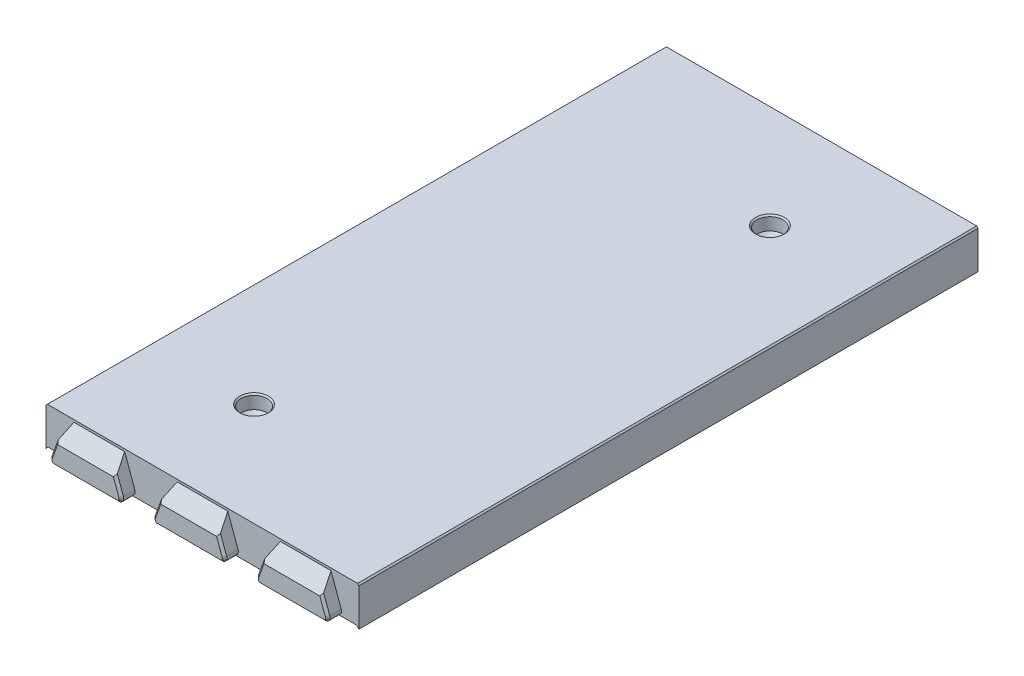
SolidWorks part; units mm, degrees
ref_plane "Front Plane" through (0, 0, 0) normal (0, 0, 1) x (1, 0, 0)
ref_plane "Top Plane" through (0, 0, 0) normal (0, 1, 0) x (1, 0, 0)
ref_plane "Right Plane" through (0, 0, 0) normal (1, 0, 0) x (0, 0, -1)
sketch "Sketch1" plane through (0, 0, 0) normal (0, 0, 1) x (1, 0, 0)
  line L0 (0, 0) -> (0, 8) construction
  line L1 (-34.125, 0) -> (0, 0) construction
  line L2 (-34.125, 0) -> (-34.125, 8)
  line L3 (-34.125, 8) -> (34.125, 8)
  line L5 (-34.125, 0) -> (-32.125, 0)
  line L6 (-32.125, 0) -> (-32.125, 6)
  line L7 (-32.125, 6) -> (32.125, 6)
  line L9 (32.125, 0) -> (32.125, 6)
  line L10 (34.125, 0) -> (32.125, 0)
  line L11 (34.125, 0) -> (34.125, 8)
  point P8 (0, 6)
  dimension "D2" = 6
  dimension "D1" = 34.125
  dimension "D3" = 2
  dimension "D4" = 2
extrude "Boss-Extrude1" add sketch "Sketch1" against normal blind 67.5
sketch "Sketch7" plane through (0, 0, 0) normal (0, 0, 1) x (1, 0, 0)
  line L2 (-32.125, 0) -> (32.125, 0)
  line L13 (-32.125, 0) -> (-32.125, 6)
  line L15 (-32.125, 6) -> (32.125, 6)
  line L16 (32.125, 0) -> (32.125, 6)
  line M3 (-32.125, 0) -> (-32.125, 6)
  line M4 (-32.125, 6) -> (32.125, 6)
  line M5 (32.125, 6) -> (32.125, 0)
extrude "Boss-Extrude7" add sketch "Sketch7" against normal blind 1 contours M4 M3 | M5 region at (0, 3, 0)
sketch "Sketch2" plane through (0, 0, 0) normal (0, 0, 1) x (1, 0, 0)
  line L14 (17.1618, 8) -> (14.25, 0)
  line L15 (34.125, 8) -> (-34.125, 8) construction
  line L16 (-34.125, 0) -> (34.125, 0) construction
  line L17 (14.25, 0) -> (30.75, 0)
  line L18 (17.1618, 8) -> (27.8382, 8)
  line L19 (-34.125, 0) -> (34.125, 0) construction
  line L21 (27.8382, 8) -> (30.75, 0)
  line L24 (11.25, 0) -> (11.25, 8) construction
  line L27 (-5.3382, 8) -> (-8.25, 0)
  line L28 (-5.3382, 8) -> (5.3382, 8)
  line L29 (-8.25, 0) -> (8.25, 0)
  line L30 (5.3382, 8) -> (8.25, 0)
  line L31 (-27.8382, 8) -> (-30.75, 0)
  line L32 (-27.8382, 8) -> (-17.1618, 8)
  line L33 (-30.75, 0) -> (-14.25, 0)
  line L34 (-17.1618, 8) -> (-14.25, 0)
  line L39 (17.1618, 8) -> (-5.3382, 8) construction
  line L40 (33.75, 8) -> (33.75, 0) construction
  line L41 (34.125, 0) -> (34.125, 8) construction
  line L42 (-33.75, 8) -> (-33.75, 0) construction
  line L43 (-34.125, 8) -> (-34.125, 0) construction
  point P22 (22.5, 8)
  point P23 (0, 8)
  dimension "D1" = 70
  dimension "D2" = 0.375
  dimension "D3" = 3
  dimension "D4" = 3
  dimension "D5" = 70
  dimension "D7" = 22.5
  dimension "D8" = 22.5
  dimension "D9" = 0.375
  dimension "D10" = 16.5
  dimension "D11" = 8
  dimension "D6" = 3
extrude "Boss-Extrude4" add sketch "Sketch2" along normal blind 3
sketch "Sketch8" plane through (0, 0, 0) normal (0, -1, 0) x (1, 0, 0)
  line L0 (-34.125, -22.5) -> (34.125, -22.5) construction
  line L2 (34.125, -67.5) -> (34.125, 0) construction
  line L3 (-34.125, 0) -> (-30.75, 0) construction
  line L4 (-32.75, -24.9559) -> (-32.75, -20.0441)
  line L5 (-32.75, -20.0441) -> (-28.75, -21.5)
  line L6 (-28.75, -21.5) -> (-28.75, -23.5)
  line L7 (-32.75, -67.5) -> (-32.75, -65.0441)
  line L8 (-32.75, -65.0441) -> (-28.75, -66.5)
  line L9 (-28.75, -66.5) -> (-28.75, -67.5)
  line L10 (-32.125, -67.5) -> (32.125, -67.5) construction
  line L11 (-28.75, -67.5) -> (-32.75, -67.5)
  line L12 (-32.75, -24.9559) -> (-28.75, -23.5)
  line L13 (0, -67.5) -> (0, 0) construction
  line L23 (-34.125, -67.5) -> (-34.125, 0) construction
  line L24 (32.75, -24.9559) -> (28.75, -23.5)
  line L25 (28.75, -21.5) -> (28.75, -23.5)
  line L26 (32.75, -20.0441) -> (28.75, -21.5)
  line L27 (32.75, -24.9559) -> (32.75, -20.0441)
  line L28 (-34.125, -67.5) -> (-32.125, -67.5) construction
  line L29 (28.75, -67.5) -> (32.75, -67.5)
  line L30 (28.75, -66.5) -> (28.75, -67.5)
  line L31 (32.75, -65.0441) -> (28.75, -66.5)
  line L32 (32.75, -67.5) -> (32.75, -65.0441)
  point P19 (-28.75, -22.5)
  point P32 (28.75, -22.5)
  dimension "D1" = 22.5
  dimension "D3" = 70
  dimension "D4" = 4
  dimension "D5" = 1.375
  dimension "D6" = 4
  dimension "D7" = 70
  dimension "D8" = 1
  dimension "D9" = 1
extrude "Boss-Extrude8" add sketch "Sketch8" against normal up to next and the other way blind 2
chamfer "Chamfer4" distance 0.5 angle 45 14 edges at (-28.75, -2, -67) (-30.75, -2, -65.7721) (-32.75, -2, -66.2721) (-30.75, -2, -24.2279) (-28.75, -2, -22.5) (-30.75, -2, -20.7721) (28.75, -2, -22.5) (30.75, -2, -24.2279) (30.75, -2, -20.7721) (32.75, -2, -22.5) (28.75, -2, -67) (32.75, -2, -66.2721) (30.75, -2, -65.7721) (-32.75, -2, -22.5)
fillet "Fillet4" radius 1 6 edges at (-30.75, 0, 1.5) (-14.25, 0, 1.5) (-8.25, 0, 1.5) (8.25, 0, 1.5) (14.25, 0, 1.5) (30.75, 0, 1.5)
chamfer "Chamfer6" distance 0.5 angle 45 15 edges at (15.9501, 4.671, 3) (29.0499, 4.671, 3) (22.5, 0, 3) (-29.0499, 4.671, 3) (-22.5, 0, 3) (-15.9501, 4.671, 3) (-6.5499, 4.671, 3) (6.5499, 4.671, 3) (0, 0, 3) (-30.141, 0.4264, 3) (-14.859, 0.4264, 3) (-7.641, 0.4264, 3) (7.641, 0.4264, 3) (14.859, 0.4264, 3) (30.141, 0.4264, 3)
fillet "Fillet2" radius 2 23 edges at (0, 6, -1) (-32.125, 3, -65.2716) (-30.4375, 6, -65.8858) (-28.75, 6, -67) (-32.125, 3, -1) (-30.4375, 6, -20.8858) (-32.125, 3, -20.2716) (-32.125, 6, -45) (-28.75, 6, -22.5) (-30.4375, 6, -24.1142) (-32.125, 3, -24.7284) (32.125, 6, -10.6358) (32.125, 3, -1) (-32.125, 6, -10.6358) (32.125, 3, -24.7284) (32.125, 3, -20.2716) (32.125, 3, -65.2716) (28.75, 6, -67) (30.4375, 6, -65.8858) (30.4375, 6, -20.8858) (28.75, 6, -22.5) (32.125, 6, -45) (30.4375, 6, -24.1142)
mirror "Mirror2" about plane through (0, 0, -67.5) normal (0, 0, 1) of "Fillet4", "Boss-Extrude1", "Boss-Extrude7", "Boss-Extrude4", "Boss-Extrude8", "Chamfer4", "Fillet2", "Chamfer6"
sketch "Sketch9" plane through (0, 0, 0) normal (0, 1, 0) x (1, 0, 0)
  line L16 (0, 67.5) -> (0, 138) construction
  line L17 (-34.125, 67.5) -> (34.125, 67.5) construction
  line L18 (-34.125, 70.4563) -> (-34.125, 64.5437) construction
  line L20 (34.125, 135) -> (34.125, 0) construction
  line L24 (4.8061, 138) -> (-4.8061, 138) construction
  circle A3 centre (-11.25, 112.5) radius 5
  circle A4 centre (11.25, 112.5) radius 5
  circle A5 centre (11.25, 22.5) radius 5
  circle A6 centre (-11.25, 22.5) radius 5
  point P23 (0, 67.5)
  point P24 (0, 67.5)
  dimension "D4" = 10
  dimension "D1" = 45
  dimension "D2" = 11.25
extrude "Boss-Extrude9" add sketch "Sketch9" along normal up to next
fillet "Fillet3" radius 3 4 edges at (-11.25, 6, -117.5) (-11.25, 6, -27.5) (11.25, 6, -27.5) (11.25, 6, -117.5)
sketch "Sketch10" plane through (0, 0, 0) normal (0, 1, 0) x (1, 0, 0)
  circle A0 centre (-11.25, 112.5) radius 1.85 construction
  circle A1 centre (-11.25, 22.5) radius 1.85
  circle A2 centre (11.25, 22.5) radius 1.85 construction
  circle A3 centre (11.25, 112.5) radius 1.85
  circle A7 centre (-11.25, 112.5) radius 5 construction
  circle A11 centre (-11.25, 112.5) radius 5 construction
  dimension "D1" = 3.7
extrude "Cut-Extrude2" cut sketch "Sketch10" along normal through all
sketch "Sketch11" plane through (0, 8, 0) normal (0, 1, 0) x (1, 0, 0)
  circle A0 centre (11.25, 112.5) radius 2.85
  circle A3 centre (-11.25, 22.5) radius 2.85
  dimension "D1" = 5.7
extrude "Cut-Extrude3" cut sketch "Sketch11" against normal blind 3
chamfer "Chamfer7" distance 1 angle 45 2 edges at (-11.25, 5, -20.65) (11.25, 5, -110.65)
sketch "Sketch12" plane through (0, 0, 0) normal (1, 0, 0) x (0, 0, -1)
  line L0 (0, 7.5) -> (-3, 4.5)
  line L1 (-3, 1.171) -> (-3, 8) construction
  line L2 (-3, 4.5) -> (-3, 7.5)
  line L3 (-3, 7.5) -> (0, 7.5) construction
  line L4 (67.5, 8) -> (67.5, 0) construction
  line L5 (135, 8) -> (0, 8) construction
  line L6 (135, 0) -> (0, 0) construction
  line L8 (138, 4.5) -> (138, 7.5)
  line L9 (135, 7.5) -> (138, 4.5)
  line L10 (0, 0) -> (0, 8) construction
  line L11 (-3, 8) -> (-2.5, 8) construction
  line L12 (-3, 7.5) -> (-3, 8)
  line L13 (-3, 8) -> (0, 8)
  line L14 (0, 8) -> (0, 7.5)
  line L15 (138, 7.5) -> (135, 7.5) construction
  line L16 (135, 8) -> (135, 7.5)
  line L17 (138, 8) -> (135, 8)
  line L18 (138, 7.5) -> (138, 8)
  dimension "D1" = 45
  dimension "D2" = 3
  dimension "D3" = 0.5
extrude "Cut-Extrude4" cut sketch "Sketch12" against normal through all both and the other way through all
sketch "Sketch13" plane through (0, 0, -135) normal (0, 0, -1) x (-1, 0, 0)
  line L0 (-33.625, 0) -> (-34.125, -0.5)
  line L1 (-29.3219, 0) -> (-34.125, 0) construction
  line L2 (-34.125, -0.5) -> (-34.125, 0)
  line L3 (-34.125, 0) -> (-33.625, 0)
  line L4 (0, 0) -> (0, 8) construction
  line L5 (-34.125, 8) -> (34.125, 8) construction
  line L6 (34.125, 0) -> (33.625, 0)
  line L7 (34.125, -0.5) -> (34.125, 0)
  line L8 (33.625, 0) -> (34.125, -0.5)
  dimension "D1" = 0.5
  dimension "D2" = 0.5
extrude "Boss-Extrude10" add sketch "Sketch13" against normal up to surface (135 mm away) up to face at (0, 3.072, 0)
chamfer "Chamfer8" distance 0.3 angle 45 4 edges at (-34.125, 8, -67.5) (34.125, 8, -67.5) (-11.25, 8, -19.65) (11.25, 8, -109.65)
